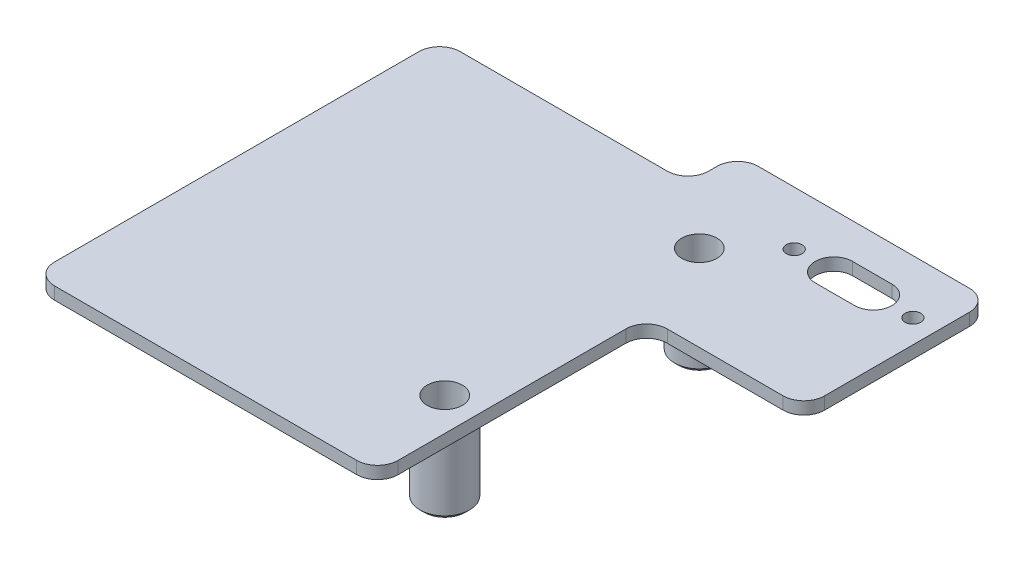
SolidWorks part; units mm, degrees
ref_plane "Front Plane" through (0, 0, 0) normal (0, 0, 1) x (1, 0, 0)
ref_plane "Top Plane" through (0, 0, 0) normal (0, 1, 0) x (1, 0, 0)
ref_plane "Right Plane" through (0, 0, 0) normal (1, 0, 0) x (0, 0, -1)
sketch "Sketch1" plane through (0, 0, 0) normal (0, 1, 0) x (1, 0, 0)
  line L0 (0, 0) -> (83, 0)
  line L1 (83, 0) -> (83, 65)
  line L2 (83, 65) -> (121, 65)
  line L3 (121, 65) -> (121, 110)
  line L4 (121, 110) -> (0, 110)
  line L5 (0, 110) -> (0, 0)
  line L6 (0, 55) -> (121, 55) construction
  line L7 (75, 85.75) -> (75, 24.25) construction
  point P11 (75, 55)
  point P13 (75, 85.75)
  point P14 (75, 24.25)
  dimension "D1" = 121
  dimension "D2" = 110
  dimension "D3" = 38
  dimension "D4" = 65
  dimension "D5" = 61.5
  dimension "D6" = 8
extrude "plate" add sketch "Sketch1" along normal blind 3
sketch "Sketch2" plane through (0, 3, 0) normal (0, 1, 0) x (1, 0, 0)
  circle A0 centre (75, 85.75) radius 6
  circle A1 centre (75, 24.25) radius 6
  dimension "D1" = 12
extrude "mount posts" add sketch "Sketch2" against normal blind 22
sketch "Sketch3" plane through (0, 3, 0) normal (0, 1, 0) x (1, 0, 0)
  circle A0 centre (75, 85.75) radius 4.25
  circle A1 centre (75, 24.25) radius 4.25
  dimension "D1" = 8.5
extrude "mount cbore" cut sketch "Sketch3" against normal blind 19.5
hole_wizard "#8 Clearance Hole1" positions "Sketch4" profile "Sketch5" hole size "#8" standard "ANSI Inch" end condition through all
sketch "Sketch4" plane through (0, -16.5, 0) normal (0, 1, 0) x (1, 0, 0)
  circle A0 centre (75, 24.25) radius 4.25 construction
  circle A1 centre (75, 85.75) radius 4.25 construction
  point P0 (75, 85.75)
  point P2 (75, 24.25)
sketch "Sketch5" plane through (75, -16.5, -85.75) normal (1, 0, 0) x (0, 0, 1)
  line L0 (0, 0) -> (0, 2.5)
  line L1 (0, 2.5) -> (2.2479, 2.5)
  line L2 (2.2479, 2.5) -> (2.2479, 0)
  line L5 (2.2479, 0) -> (0, 0)
  line L11 (0, -6.35) -> (0, 107.95) construction
  dimension "Thru Hole Dia." = 4.4958
  dimension "Thru Hole Depth" = 2.5
ref_plane "mid plane" through (0, 0, -55) normal (0, 0, -1) x (1, 0, 0)
sketch "Sketch8" plane through (0, 0, -55) normal (0, 0, -1) x (1, 0, 0)
  line L0 (45.25, 0) -> (46.85, 0)
  line L1 (0, 0) -> (121, 0) construction
  line L2 (45.25, 0) -> (43.5, 21)
  line L3 (43.5, 21) -> (45.1, 21)
  line L4 (45.1, 21) -> (46.85, 0)
  line L5 (40, 0) -> (40, 41.9178) construction
  point P9 (44.3, 21)
  dimension "D1" = 1.6
  dimension "D2" = 3.5
  dimension "D3" = 21
  dimension "D4" = 5.25
  dimension "D5" = 40
revolve "foot" add sketch "Sketch8" angle 360 about L5
fillet "Fillet1" radius 1.5 2 edges at (40, 0, -49.75) (40, 0, -48.15)
sketch "Sketch7" plane through (0, 3, 0) normal (0, 1, 0) x (1, 0, 0)
  line L0 (91.7375, 97) -> (110.2625, 97) construction
  line L1 (121, 65) -> (121, 110) construction
  line L3 (101, 88.5) -> (101, 105.5) construction
  line L4 (96.2375, 101.5) -> (105.7625, 101.5)
  line L5 (81, 105.5) -> (121, 105.5) construction
  line L6 (81, 105.5) -> (81, 88.5) construction
  line L7 (81, 88.5) -> (121, 88.5) construction
  line L8 (121, 105.5) -> (121, 88.5) construction
  line L9 (81, 105.5) -> (121, 88.5) construction
  line L10 (81, 88.5) -> (121, 105.5) construction
  line L11 (96.2375, 92.5) -> (105.7625, 92.5)
  line L13 (121, 110) -> (0, 110) construction
  circle A0 centre (96.2375, 97) radius 4.5 construction
  circle A1 centre (105.7625, 97) radius 4.5 construction
  arc A2 (96.2375, 101.5) -> (96.2375, 92.5) centre (96.2375, 97) ccw
  arc A3 (105.7625, 101.5) -> (105.7625, 92.5) centre (105.7625, 97) cw
  circle A4 centre (115.34, 97) radius 1.9
  circle A5 centre (86.66, 97) radius 1.9
  point P16 (101, 97)
  dimension "D2" = 9.525
  dimension "D5" = 9
  dimension "D6" = 3.8
  dimension "D1" = 13
  dimension "D3" = 40
  dimension "D4" = 17
  dimension "D7" = 28.68
extrude "terminal strip" cut sketch "Sketch7" against normal through all
sketch "Sketch9" plane through (0, 3, 0) normal (0, 1, 0) x (1, 0, 0)
  line L0 (0, 98) -> (60, 98)
  line L1 (0, 110) -> (0, 0) construction
  line L2 (60, 98) -> (60, 110)
  line L3 (121, 110) -> (0, 110) construction
  line L4 (60, 110) -> (0, 110)
  line L5 (0, 110) -> (0, 98)
  dimension "D1" = 60
  dimension "D2" = 12
extrude "wiring relief" cut sketch "Sketch9" against normal through all
chamfer "Chamfer1" distance 3 angle 45 2 edges at (75, -16.5, -81.5) (75, -16.5, -20)
chamfer "Chamfer2" distance 1 angle 45 2 edges at (75, -19, -18.25) (75, -19, -79.75)
fillet "Fillet2" radius 5 8 edges at (121, 1.5, -110) (121, 1.5, -65) (83, 1.5, -65) (83, 1.5, 0) (0, 1.5, 0) (60, 1.5, -110) (60, 1.5, -98) (0, 1.5, -98)
fillet "Fillet3" radius 1.5 2 edges at (75, 0, -79.75) (75, 0, -18.25)
